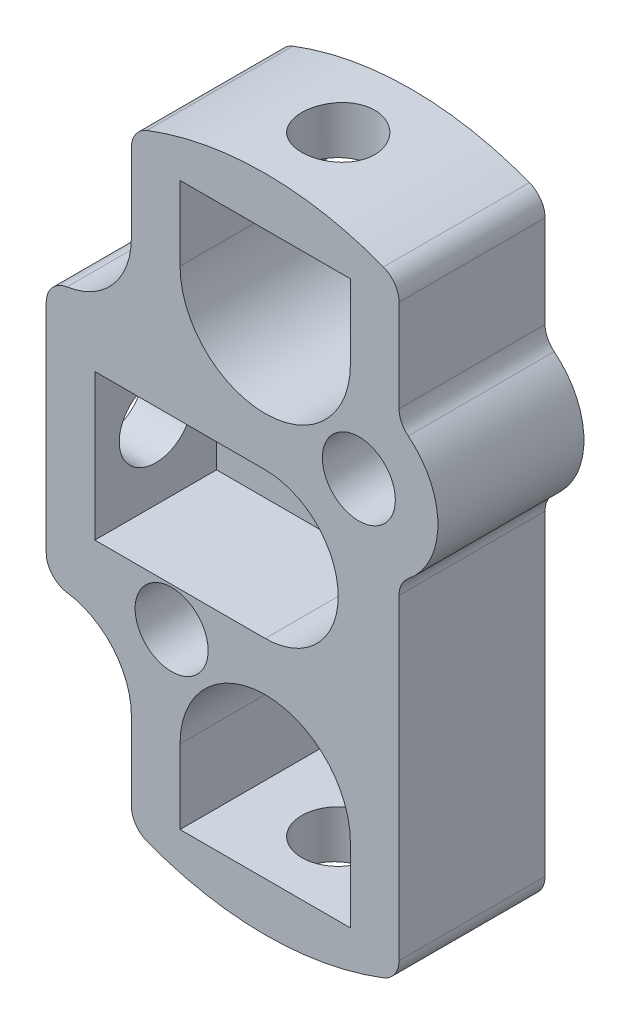
SolidWorks part; units mm, degrees
ref_plane "Plan de face" through (0, 0, 0) normal (0, 0, 1) x (1, 0, 0)
ref_plane "Plan de dessus" through (0, 0, 0) normal (0, 1, 0) x (1, 0, 0)
ref_plane "Plan de droite" through (0, 0, 0) normal (1, 0, 0) x (0, 0, -1)
sketch "Esquisse1" plane through (0, 0, 0) normal (0, 0, 1) x (1, 0, 0)
  line L0 (0, -1000) -> (0, 49000) construction
  line L1 (-3.5, 11.55) -> (3.5, 11.55)
  line L2 (-1000, 0) -> (49000, 0) construction
  line L3 (-3.5, -11.55) -> (3.5, -11.55)
  line L4 (-3.5, 8.5) -> (-3.5, 11.55)
  line L5 (3.5, 8.5) -> (3.5, 11.55)
  line L6 (3.5, -8.5) -> (3.5, -11.55)
  line L7 (-3.5, -8.5) -> (-3.5, -11.55)
  line L8 (-2.0275, -5.6471) -> (-5.1962, -3) construction
  line L9 (0, -3) -> (-7, -3)
  line L10 (0, -3) -> (0, 3) construction
  line L11 (0, 3) -> (-7, 3)
  line L12 (-7, -3) -> (-7, 3)
  line L13 (0, 0) -> (-32055.7157, -38372.2698) construction
  line L14 (5.5, -12.3836) -> (5.5, 12.3836) construction
  line L15 (-9, 4.4479) -> (-9, -4.4479)
  line L16 (-5.5, 11.7155) -> (-5.5, 8.5)
  line L17 (-5.5, -11.7155) -> (-5.5, -8.5)
  line L18 (5.5, 11.7155) -> (5.5, 7.9247)
  line L19 (5.5, 1.2847) -> (5.5, -11.7155)
  circle A0 centre (0, 0) radius 13.55 construction
  circle A1 centre (0, 0) radius 3 construction
  circle A2 centre (0, 0) radius 6 construction
  arc A3 (-3.5, 8.5) -> (3.5, 8.5) centre (0, 8.5) ccw
  arc A4 (-3.5, -8.5) -> (3.5, -8.5) centre (0, -8.5) cw
  arc A5 (0, 3) -> (0, -3) centre (0, 0) cw
  circle A6 centre (-3.8467, -4.6047) radius 1.5
  circle A7 centre (3.8467, 4.6047) radius 1.5
  arc A8 (-5.5, 8.5) -> (-8.1454, 5.4373) centre (-8.5956, 8.5) cw
  arc A9 (-4.8586, 12.649) -> (4.8586, 12.649) centre (0, 0) cw
  arc A10 (-4.8586, -12.649) -> (4.8586, -12.649) centre (0, 0) ccw
  arc A11 (-5.5, -8.5) -> (-8.1454, -5.4373) centre (-8.5956, -8.5) ccw
  arc A12 (-8.1454, -5.4373) -> (-9, -4.4479) centre (-8, -4.4479) cw
  arc A13 (-9, 4.4479) -> (-8.1454, 5.4373) centre (-8, 4.4479) cw
  circle A14 centre (3.8467, 4.6047) radius 3.25 construction
  arc A15 (5.8757, 7.1435) -> (5.8757, 2.0658) centre (3.8467, 4.6047) cw
  arc A16 (5.8757, 2.0658) -> (5.5, 1.2847) centre (6.5, 1.2847) ccw
  arc A17 (5.5, 7.9247) -> (5.8757, 7.1435) centre (6.5, 7.9247) ccw
  arc A18 (5.5, 11.7155) -> (4.8586, 12.649) centre (4.5, 11.7155) ccw
  arc A19 (-5.5, 11.7155) -> (-4.8586, 12.649) centre (-4.5, 11.7155) cw
  arc A20 (4.8586, -12.649) -> (5.5, -11.7155) centre (4.5, -11.7155) ccw
  arc A21 (-4.8586, -12.649) -> (-5.5, -11.7155) centre (-4.5, -11.7155) cw
  point P4 (0, 13.55)
  point P9 (0, 11.55)
  point P21 (0, 5)
  point P22 (0, 3)
  point P41 (6.8467, 0)
  point P48 (-9, 0)
  point P50 (-9, -5.4309)
  point P53 (-9, 5.4309)
  point P56 (5.5, 0)
  point P59 (5.6739, -12.3048)
  point P61 (5.5, 1.8066)
  point P64 (5.5, 7.4027)
  point P69 (-5.5, 12.3836)
  point P75 (-5.5, -12.3836)
  dimension "D1" = 27.1
  dimension "D2" = 6
  dimension "D4" = 12
  dimension "D6" = 7
  dimension "D7" = 2
  dimension "D8" = 3
  dimension "D10" = 3
  dimension "D12" = 1
  dimension "D14" = 6.5
  dimension "D15" = 1
  dimension "D16" = 1
  dimension "D3" = 2
  dimension "D5" = 7
  dimension "D9" = 2
  dimension "D11" = 2
  dimension "D13" = 2
extrude "Boss.-Extru.1" add sketch "Esquisse1" along normal blind 5 contours A3 L4 L1 L5 A1 L7 A4 L6 L3 region at (-8.5182, 4.8956, 0)
extrude "Boss.-Extru.2" add sketch "Esquisse1<3>" against normal blind 1 contours A3 L4 L1 L5 A1 L7 A4 L6 L3 | A1 | A5 L11 L12 L9 region at (-4.6298, 0, 0) region at (0, 0, 0) region at (-8.5182, 4.8956, 0)
sketch "Esquisse1<3>" plane through (0, 0, 0) normal (0, 0, 1) x (1, 0, 0) same geometry as "Esquisse1"
sketch "Esquisse2" plane through (0, 11.55, 0) normal (0, -1, 0) x (1, 0, 0)
  line L0 (-3.5, 5) -> (3.5, -1) construction
  circle A0 centre (0, 2) radius 1.5
  dimension "D1" = 3
extrude "Enlèv. mat.-Extru.2" cut sketch "Esquisse2" against normal through all
mirror "Symétrie1" about plane through (0, 0, 0) normal (0, 1, 0) of "Enlèv. mat.-Extru.2"
sketch "Esquisse3" plane through (-7, 0, 0) normal (1, 0, 0) x (0, 0, -1)
  line L0 (-5, 3) -> (0, -3) construction
  circle A0 centre (-2.5, 0) radius 1.5
  dimension "D1" = 3
extrude "Enlèv. mat.-Extru.3" cut sketch "Esquisse3" against normal through all
